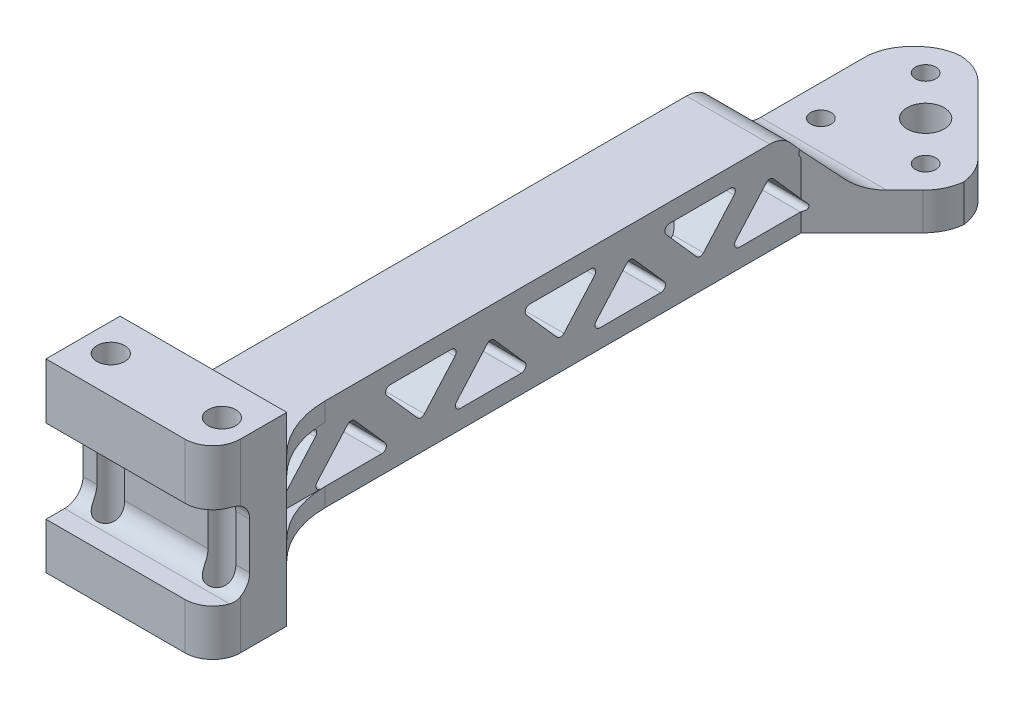
SolidWorks part; units mm, degrees
material "ABS PC"
ref_plane "Front Plane" through (0, 0, 0) normal (0, 0, 1) x (1, 0, 0)
ref_plane "Top Plane" through (0, 0, 0) normal (0, 1, 0) x (1, 0, 0)
ref_plane "Right Plane" through (0, 0, 0) normal (1, 0, 0) x (0, 0, -1)
sketch "Sketch1" plane through (0, 0, 0) normal (0, 1, 0) x (1, 0, 0)
  line L0 (0, 90.435) -> (0, 0)
  line L1 (0, 0) -> (15, 0)
  line L2 (18, 3) -> (18, 8)
  line L3 (18, 8) -> (11.9289, 14.0711)
  line L4 (9, 21.1421) -> (9, 72.565)
  line L5 (9, 72.565) -> (9, 86) construction
  line L6 (3, 4) -> (15, 4) construction
  line L7 (0, 90.435) -> (3.3076, 93.7426)
  line L8 (3.3076, 93.7426) -> (6.9142, 93.7426)
  line L9 (6.9142, 93.7426) -> (17.0459, 83.6109)
  line L10 (17.0459, 83.6109) -> (17.0459, 80.6109)
  line L11 (17.0459, 80.6109) -> (9, 72.565)
  line L12 (9, 86) -> (13.2426, 81.7574) construction
  line L13 (4.7574, 90.2426) -> (9, 86) construction
  line L14 (9, 86) -> (3.3431, 80.3431) construction
  circle A0 centre (9, 86) radius 6 construction
  circle A1 centre (9, 86) radius 8 construction
  circle A2 centre (3, 4) radius 1.5
  circle A3 centre (15, 4) radius 1.5
  arc A4 (18, 3) -> (15, 0) centre (15, 3) cw
  circle A5 centre (13.2426, 81.7574) radius 1.1
  circle A6 centre (4.7574, 90.2426) radius 1.1
  circle A7 centre (3.3431, 80.3431) radius 1.1
  circle A8 centre (9, 86) radius 2
  arc A9 (11.9289, 14.0711) -> (9, 21.1421) centre (19, 21.1421) cw
  point P17 (18, 0)
  dimension "D8" = 3
  dimension "D9" = 3
  dimension "D11" = 16
  dimension "D12" = 12
  dimension "D14" = 90
  dimension "D16" = 2.2
  dimension "D21" = 4
  dimension "D24" = 10
  dimension "D1" = 18
  dimension "D2" = 8
  dimension "D3" = 12
  dimension "D4" = 3
  dimension "D5" = 4
  dimension "D6" = 45
  dimension "D7" = 9
  dimension "D10" = 82
  dimension "D13" = 45
  dimension "D15" = 90
  dimension "D17" = 3.5
  dimension "D18" = 45
  dimension "D19" = 3.5
  dimension "D20" = 3.5
  dimension "D22" = 4
  dimension "D23" = 3
extrude "Boss-Extrude1" add sketch "Sketch1" along normal blind 10
sketch "Sketch2" plane through (0, 0, 0) normal (-1, 0, 0) x (0, 0, 1)
  line L0 (-96.1782, 8) -> (2.5289, 8) construction
  line L1 (2.5289, 8) -> (2.5289, 7) construction
  line L2 (2.5289, 7) -> (-96.1782, 7) construction
  line L3 (-96.1782, 7) -> (-96.1782, 5) construction
  line L4 (-96.1782, 5) -> (2.5289, 5) construction
  line L5 (2.5289, 5) -> (2.5289, 3) construction
  line L6 (2.5289, 3) -> (-96.1782, 3) construction
  line L7 (-96.1782, 3) -> (-96.1782, 2) construction
  line L8 (-96.1782, 2) -> (2.5289, 2) construction
  line L9 (-90.435, 10) -> (0, 10) construction
  line L10 (-90.435, 0) -> (0, 0) construction
  line L11 (-8, 8) -> (-8, 2)
  line L12 (-8, 2) -> (-13.3, 2)
  line L13 (-13.3, 2) -> (-8, 8)
  line L14 (-20.8361, 8) -> (-12.0028, 8)
  line L15 (-12.0028, 8) -> (-16.4195, 3)
  line L16 (-16.4195, 3) -> (-20.8361, 8)
  line L17 (-28.3723, 2) -> (-19.539, 2)
  line L18 (-19.539, 2) -> (-23.9556, 7)
  line L19 (-23.9556, 7) -> (-28.3723, 2)
  line L20 (-27.0751, 8) -> (-31.4918, 3)
  line L21 (-31.4918, 3) -> (-35.9084, 8)
  line L22 (-35.9084, 8) -> (-27.0751, 8)
  line L23 (-42.1474, 8) -> (-46.5641, 3)
  line L24 (-46.5641, 3) -> (-50.9807, 8)
  line L25 (-50.9807, 8) -> (-42.1474, 8)
  line L26 (-57.2197, 8) -> (-61.6363, 3)
  line L27 (-61.6363, 3) -> (-66.053, 8)
  line L28 (-66.053, 8) -> (-57.2197, 8)
  line L29 (-39.0279, 7) -> (-43.4446, 2)
  line L30 (-34.6112, 2) -> (-39.0279, 7)
  line L31 (-43.4446, 2) -> (-34.6112, 2)
  line L32 (-54.1002, 7) -> (-58.5169, 2)
  line L33 (-49.6835, 2) -> (-54.1002, 7)
  line L34 (-58.5169, 2) -> (-49.6835, 2)
  line L35 (-69.1725, 7) -> (-73.5892, 2)
  line L36 (-64.7558, 2) -> (-69.1725, 7)
  line L37 (-73.5892, 2) -> (-64.7558, 2)
  line L38 (0, 10) -> (0, 0) construction
  line L39 (-77, 8) -> (-77, 2)
  line L40 (-77, 2) -> (-71.7, 8)
  line L41 (-71.7, 8) -> (-77, 8)
  dimension "D1" = 2
  dimension "D2" = 2
  dimension "D3" = 1
  dimension "D4" = 1
  dimension "D5" = 2
  dimension "D6" = 5.3
  dimension "D7" = 3
  dimension "D8" = 3
  dimension "D11" = 8
  dimension "D12" = 77
  dimension "D13" = 3
  dimension "D14" = 3
  dimension "D9" = 4
  dimension "D10" = 4
extrude "Cut-Extrude1" cut sketch "Sketch2" against normal up to next
sketch "Sketch3" plane through (9, 0, 0) normal (1, 0, 0) x (0, 0, -1)
  line L0 (8, 8) -> (21.1421, 8)
  line L1 (21.1421, 10) -> (21.1421, 3.8149) construction
  line L2 (21.1421, 8) -> (21.1421, 2)
  line L3 (21.1421, 2) -> (8, 2)
  line L4 (8, 2) -> (8, 8)
extrude "Cut-Extrude2" cut sketch "Sketch3" along normal blind 30
fillet "Fillet2" radius 0.5 29 edges at (4.5, 2, -13.3) (9, 2, -8) (4.5, 8, -12.0028) (4.5, 3, -16.4195) (4.5, 8, -20.8361) (4.5, 2, -19.539) (4.5, 2, -28.3723) (4.5, 7, -23.9556) (4.5, 8, -27.0751) (4.5, 3, -31.4918) (4.5, 8, -35.9084) (4.5, 7, -39.0279) (4.5, 2, -34.6112) (4.5, 2, -43.4446) (4.5, 8, -42.1474) (4.5, 3, -46.5641) (4.5, 8, -50.9807) (4.5, 2, -58.5169) (4.5, 7, -54.1002) (4.5, 2, -49.6835) (4.5, 8, -57.2197) (4.5, 3, -61.6363) (4.5, 8, -66.053) (4.5, 2, -64.7558) (4.5, 7, -69.1725) (5.0121, 2, -73.5892) (4.5, 8, -71.7) (6.7175, 2, -77) (6.7175, 8, -77)
sketch "Sketch6" plane through (0, 10, 0) normal (0, 1, 0) x (1, 0, 0)
  line L0 (18, 8) -> (0, 8)
  line L1 (0, 90.435) -> (0, 0) construction
  line L2 (0, 8) -> (0, 0)
  line L3 (0, 0) -> (15, 0) construction
  line L4 (18, 3) -> (18, 8) construction
  line L5 (0, 0) -> (15, 0)
  line L6 (18, 3) -> (18, 8)
  circle A0 centre (3, 4) radius 1.5 construction
  circle A1 centre (15, 4) radius 1.5 construction
  arc A2 (15, 0) -> (18, 3) centre (15, 3) ccw construction
  circle A3 centre (3, 4) radius 1.5
  circle A4 centre (15, 4) radius 1.5
  arc A5 (15, 0) -> (18, 3) centre (15, 3) ccw
extrude "Boss-Extrude2" add sketch "Sketch6" along normal blind 10
sketch "Sketch7" plane through (0, 0, 0) normal (-1, 0, 0) x (0, 0, 1)
  line L0 (0, 20) -> (0, 0) construction
  line L1 (0, 14) -> (-4, 14)
  line L2 (0, 14) -> (0, 5)
  line L3 (0, 5) -> (-4, 5)
  line L4 (-4, 14) -> (-4, 5)
  line L5 (-90.435, 0) -> (0, 0) construction
  line L6 (-8, 20) -> (0, 20) construction
  dimension "D1" = 5
  dimension "D2" = 4
  dimension "D3" = 6
extrude "Cut-Extrude3" cut sketch "Sketch7" against normal through all
sketch "Sketch8" plane through (0, 0, 0) normal (-1, 0, 0) x (0, 0, 1)
  line L0 (-8, 20) -> (-8, 10)
  line L1 (-8, 10) -> (-18, 10)
  line L2 (-90.435, 10) -> (-8, 10) construction
  line L3 (-18, 10) -> (-8, 20)
  dimension "D1" = 45
extrude "Boss-Extrude3" add sketch "Sketch8" against normal blind 10
sketch "Sketch9" plane through (0, 0, 0) normal (-1, 0, 0) x (0, 0, 1)
  line L0 (-77, 7.5) -> (-77, 3.3213) construction
  line L1 (-76.1253, 2.9903) -> (-72.4341, 7.169) construction
  line L2 (-72.8088, 8) -> (-76.5, 8) construction
  line L3 (-77, 7.5) -> (-77, 3.3213)
  line L4 (-76.1253, 2.9903) -> (-72.4341, 7.169)
  line L5 (-72.8088, 8) -> (-76.5, 8)
  arc A0 (-76.5, 8) -> (-77, 7.5) centre (-76.5, 7.5) ccw construction
  arc A1 (-77, 3.3213) -> (-76.1253, 2.9903) centre (-76.5, 3.3213) ccw construction
  arc A2 (-72.4341, 7.169) -> (-72.8088, 8) centre (-72.8088, 7.5) ccw construction
  arc A3 (-76.5, 8) -> (-77, 7.5) centre (-76.5, 7.5) ccw
  arc A4 (-77, 3.3213) -> (-76.1253, 2.9903) centre (-76.5, 3.3213) ccw
  arc A5 (-72.4341, 7.169) -> (-72.8088, 8) centre (-72.8088, 7.5) ccw
extrude "Boss-Extrude4" add sketch "Sketch9" against normal up to surface (9.2438 mm away) up to face at (11.3891, 5.1785, -74.954)
sketch "Sketch10" plane through (0, 0, 0) normal (-1, 0, 0) x (0, 0, 1)
  line L0 (-70.5253, 10) -> (-75.8253, 4)
  line L1 (-90.435, 10) -> (-18, 10) construction
  line L2 (-75.8253, 4) -> (-96.4392, 4)
  line L3 (-96.4392, 4) -> (-96.4392, 10)
  line L4 (-96.4392, 10) -> (-70.5253, 10)
  line L5 (-69.5472, 6.5758) -> (-72.8551, 2.831) construction
  line L6 (-90.435, 0) -> (0, 0) construction
  dimension "D1" = 3
  dimension "D2" = 4
extrude "Cut-Extrude4" cut sketch "Sketch10" against normal through all
fillet "Fillet3" radius 2 2 edges at (9, 14, -4) (9, 5, -4)
chamfer "Chamfer1" distance 7 angle 50 1 edges at (10, 15, -13) first distance on face at (10, 12.5, -12.6958)
fillet "Fillet4" radius 2 3 edges at (5.8289, 10, -13.0503) (5.8289, 15.0503, -8) (14, 10, -8)
fillet "Fillet5" radius 3 2 edges at (4.5, 10, -70.5253) (6.1302, 4, -75.8253)
fillet "Fillet7" radius 5 5 edges at (0, 2, -90.435) (3.3076, 2, -93.7426) (6.9142, 2, -93.7426) (17.0459, 2, -83.6109) (17.0459, 2, -80.6109)
sketch "Sketch12" plane through (0, 0, 0) normal (0, -1, 0) x (-1, 0, 0)
  line L0 (0, 88.364) -> (0, 0) construction
  circle A0 centre (-4.5, 61.5855) radius 1.25
  dimension "D2" = 2.5
  dimension "D1" = 4.5
  dimension "D3" = 32.15
extrude "Cut-Extrude5" cut sketch "Sketch12" against normal blind 6
